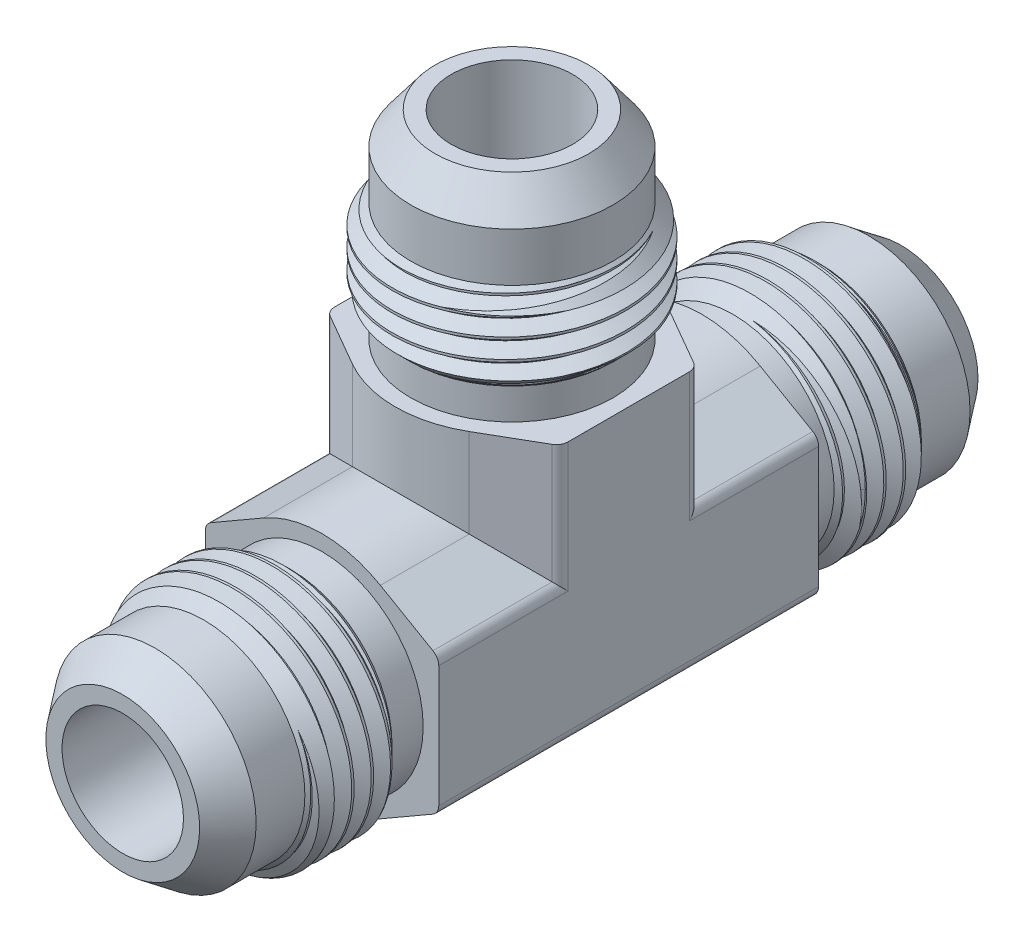
SolidWorks part; units mm, degrees
material "AISI 316 Annealed Stainless Steel Bar (SS)"
ref_plane "Front Plane" through (0, 0, 0) normal (0, 0, 1) x (1, 0, 0)
ref_plane "Top Plane" through (0, 0, 0) normal (0, 1, 0) x (1, 0, 0)
ref_plane "Right Plane" through (0, 0, 0) normal (1, 0, 0) x (0, 0, -1)
sketch "Sketch1" plane through (0, 0, 0) normal (1, 0, 0) x (0, 0, -1)
  line L0 (-31.75, -11.1125) -> (31.75, -11.1125) construction
  line L1 (31.75, -20.6375) -> (-31.75, -20.6375) construction
  line L2 (31.75, -20.6375) -> (31.75, 20.6375) construction
  line L3 (31.75, 20.6375) -> (-31.75, 20.6375) construction
  line L4 (-31.75, -20.6375) -> (-31.75, 20.6375) construction
  line L5 (31.75, -20.6375) -> (-31.75, 20.6375) construction
  line L6 (31.75, 20.6375) -> (-31.75, -20.6375) construction
  line L7 (0, -11.1125) -> (0, 20.6375) construction
  line L8 (-31.75, -4.8387) -> (-29.1209, -2.8575)
  line L9 (-15.494, -20.6375) -> (15.494, -20.6375)
  line L10 (-15.494, -20.6375) -> (-15.494, -1.5875)
  line L11 (-15.494, -1.5875) -> (15.494, -1.5875)
  line L12 (15.494, -20.6375) -> (15.494, -1.5875)
  line L13 (-15.494, -20.6375) -> (15.494, -1.5875) construction
  line L14 (-15.494, -1.5875) -> (15.494, -20.6375) construction
  line L15 (-31.75, -19.3675) -> (-15.494, -19.3675)
  line L16 (-31.75, -19.3675) -> (-31.75, -2.8575)
  line L17 (-31.75, -2.8575) -> (-15.494, -2.8575)
  line L18 (-15.494, -19.3675) -> (-15.494, -2.8575)
  line L19 (-31.75, -19.3675) -> (-15.494, -2.8575) construction
  line L20 (-31.75, -2.8575) -> (-15.494, -19.3675) construction
  line L21 (-18.034, -20.6375) -> (-25.146, -20.6375)
  line L22 (-18.034, -20.6375) -> (-18.034, -1.5875)
  line L23 (-18.034, -1.5875) -> (-25.146, -1.5875)
  line L24 (-25.146, -20.6375) -> (-25.146, -1.5875)
  line L25 (-18.034, -20.6375) -> (-25.146, -1.5875) construction
  line L26 (-18.034, -1.5875) -> (-25.146, -20.6375) construction
  line L27 (-31.75, -16.0655) -> (0, -16.0655)
  line L28 (-31.75, -16.0655) -> (-31.75, -6.1595)
  line L29 (-31.75, -6.1595) -> (0, -6.1595)
  line L30 (0, -16.0655) -> (0, -6.1595)
  line L31 (-31.75, -16.0655) -> (0, -6.1595) construction
  line L32 (-31.75, -6.1595) -> (0, -16.0655) construction
  line L33 (-31.75, -2.8575) -> (31.75, -2.8575) construction
  point P0 (0, 0)
  point P14 (-21.59, -11.1125)
  point P15 (-23.622, -11.1125)
  point P24 (-23.5585, -20.6375)
  point P25 (-15.875, -11.1125)
  point P30 (-22.0027, -20.6375)
  point P33 (31.75, -2.8575)
  dimension "Height" = 31.75
  dimension "Length" = 63.5
  dimension "Body Length" = 30.988
  dimension "Body Height" = 19.05
  dimension "Body Diameter" = 16.51
  dimension "Thread Size" = 19.05
  dimension "Space" = 2.54
  dimension "Thread Length" = 7.112
  dimension "Thread Pitch" = 1.5875
  dimension "ID" = 9.906
  dimension "Flared Angle" = 37
  dimension "Flare Height" = 1.9812
  dimension "D1" = 3.9688
sketch "Sketch2" plane through (0, 0, 0) normal (0, 0, 1) x (1, 0, 0)
  line L0 (9.525, -11.1125) -> (-9.525, -11.1125) construction
  line L1 (9.525, -20.6375) -> (-9.525, -20.6375)
  line L2 (9.525, -20.6375) -> (9.525, 20.6375)
  line L3 (9.525, 20.6375) -> (-9.525, 20.6375)
  line L4 (-9.525, -20.6375) -> (-9.525, 20.6375)
  line L5 (9.525, -20.6375) -> (-9.525, 20.6375) construction
  line L6 (9.525, 20.6375) -> (-9.525, -20.6375) construction
  circle A0 centre (0, -11.1125) radius 4.953
  point P0 (0, 0)
  point P12 (0, -16.0655)
  dimension "Width" = 19.05
sketch "Sketch3" plane through (0, 0, 0) normal (1, 0, 0) x (0, 0, -1)
  line L0 (-31.75, -11.1125) -> (0, -11.1125)
  line L1 (0, -11.1125) -> (0, -6.1595)
  line L2 (0, -6.1595) -> (-15.494, -6.1595)
  line L3 (-15.494, -20.6375) -> (-15.494, -1.5875) construction
  line L4 (-31.75, -6.1595) -> (0, -6.1595) construction
  line L5 (-15.494, -6.1595) -> (-15.494, -2.8575)
  line L6 (-15.494, -2.8575) -> (-18.034, -2.8575)
  line L7 (-31.75, -2.8575) -> (-15.494, -2.8575) construction
  line L8 (-18.034, -20.6375) -> (-18.034, -1.5875) construction
  line L9 (-18.034, -2.8575) -> (-19.304, -1.5875)
  line L10 (-18.034, -1.5875) -> (-25.146, -1.5875) construction
  line L11 (-19.304, -1.5875) -> (-23.876, -1.5875)
  line L12 (-23.876, -1.5875) -> (-25.146, -2.8575)
  line L13 (-25.146, -20.6375) -> (-25.146, -1.5875) construction
  line L14 (-25.146, -2.8575) -> (-29.1209, -2.8575)
  line L15 (-29.1209, -2.8575) -> (-31.75, -4.8387)
  line L16 (-31.75, -4.8387) -> (-31.75, -11.1125)
  dimension "D1" = 45
  dimension "D2" = 45
revolve "Revolve1" add sketch "Sketch3" angle 360 about L0
sketch "Sketch4" plane through (0, 0, 0) normal (0, 0, -1) x (-1, 0, 0)
  line L0 (-4.7625, -2.8636) -> (-9.0487, -5.3383)
  line L1 (9.525, -20.6375) -> (-9.525, -20.6375) construction
  line L2 (9.525, -20.6375) -> (9.525, -1.5875) construction
  line L3 (9.525, -1.5875) -> (-9.525, -1.5875) construction
  line L4 (-9.525, -20.6375) -> (-9.525, -1.5875) construction
  line L5 (9.525, -20.6375) -> (-9.525, -1.5875) construction
  line L6 (9.525, -1.5875) -> (-9.525, -20.6375) construction
  line L7 (0, -20.6375) -> (0, 20.6375) construction
  line L8 (-9.525, -6.1632) -> (-9.525, -16.0618)
  line L9 (-9.0488, -16.8867) -> (-4.7625, -19.3614)
  line L10 (4.7625, -19.3614) -> (9.0488, -16.8867)
  line L11 (9.525, -16.0618) -> (9.525, -6.1632)
  line L12 (9.0488, -5.3383) -> (4.7625, -2.8636)
  arc A0 (-4.7625, -2.8636) -> (4.7625, -2.8636) centre (0, -11.1125) cw
  arc A1 (-4.7625, -19.3614) -> (4.7625, -19.3614) centre (0, -11.1125) ccw
  arc A2 (9.525, -6.1632) -> (9.0488, -5.3383) centre (8.5725, -6.1632) ccw
  arc A3 (9.0488, -16.8867) -> (9.525, -16.0618) centre (8.5725, -16.0618) ccw
  arc A4 (-9.525, -16.0618) -> (-9.0488, -16.8867) centre (-8.5725, -16.0618) ccw
  arc A5 (-9.0487, -5.3383) -> (-9.525, -6.1632) centre (-8.5725, -6.1632) ccw
  point P0 (0, -11.1125)
  point P13 (9.525, -11.1125)
  point P17 (-9.525, -11.1125)
  point P20 (0, -0.114)
  point P26 (9.525, -5.6132)
  point P29 (9.525, -16.6118)
  point P32 (-9.525, -16.6118)
  point P35 (-9.525, -5.6132)
  dimension "D1" = 9.525
  dimension "D4" = 0.9525
  dimension "D2" = 120
  dimension "D3" = 120
extrude "Boss-Extrude1" add sketch "Sketch4" against normal up to vertex (15.494 mm away) up to point (0, -1.5875, 15.494)
pattern_circular "CirPattern1" count 3 every 90 about axis through (9.525, -11.1125, 0) along (-1, 0, 0) of bodies 105
combine bodies "Combine1" operation type add bodies to combine 106 107 105
sketch "Sketch5" plane through (0, 0, 0) normal (0, 0, 1) x (1, 0, 0)
  circle A0 centre (0, -11.1125) radius 4.953
extrude "Cut-Extrude1" cut sketch "Sketch5" against normal through all both and the other way through all
sketch "Sketch6" plane through (0, 20.6375, 0) normal (0, 1, 0) x (1, 0, 0)
  circle A0 centre (0, 0) radius 4.953
  dimension "D1" = 9.906
extrude "Cut-Extrude2" cut sketch "Sketch6" against normal up to vertex (31.75 mm away) up to point (0, -11.1125, 0)
ref_plane "Plane1" through (0, 0, 18.034) normal (0, 0, 1) x (1, 0, 0)
sketch "Sketch7" plane through (0, 0, 18.034) normal (0, 0, 1) x (1, 0, 0)
  circle A0 centre (0, -11.1125) radius 9.525 construction
  circle A1 centre (0, -11.1125) radius 9.525
curve "Helix/Spiral1" pitch 1.5875 height 8.6995 radius 9.525 centre (0, -11.1125, 18.034) axis (0, 0, 1) start towards (0, 1, 0)
sketch "Sketch8" plane through (0, 0, 0) normal (1, 0, 0) x (0, 0, -1)
  line L0 (-18.1332, -1.4156) -> (-16.5457, -1.4156) construction
  line L1 (-16.5457, -1.4156) -> (-17.3395, -2.7905) construction
  line L2 (-17.3395, -2.7905) -> (-18.1332, -1.4156) construction
  line L3 (-17.3395, -1.4156) -> (-17.3395, -1.5875) construction
  line L4 (-16.6449, -1.5875) -> (-18.034, -1.5875) construction
  line L5 (-17.4387, -2.6186) -> (-17.2402, -2.6186) construction
  line L6 (-17.3395, -2.6186) -> (-17.3395, -2.7905) construction
  line L7 (-17.3395, -1.5016) -> (-18.0836, -1.5016) construction
  line L8 (-16.5457, -1.4156) -> (-18.0836, -1.5016)
  line L9 (-18.0836, -1.5016) -> (-17.4387, -2.6186)
  line L10 (-17.4387, -2.6186) -> (-17.2402, -2.6186)
  line L11 (-17.2402, -2.6186) -> (-16.5457, -1.4156)
  dimension "D1" = 1.5875
  dimension "D2" = 0.1984
sweep "Cut-Sweep1" cut profiles "Sketch8" path "Helix/Spiral1" align with end faces yes
pattern_circular "CirPattern2" count 3 every 90 about axis through (9.525, -11.1125, 0) along (-1, 0, 0) of "Cut-Sweep1"
equation "\"D1@Sketch4\"=\"Width@Sketch2\"*.5"
equation "\"D4@Sketch4\"=\"Width@Sketch2\"*.05"
equation "\"D1@Sketch6\"=\"ID@Sketch1\""
equation "\"D4@Helix/Spiral1\"=\"Thread Pitch@Sketch1\""
equation "\"D3@Helix/Spiral1\"=\"Thread Length@Sketch1\"+\"Thread Pitch@Sketch1\""
equation "\"D1@Sketch8\"=\"Thread Pitch@Sketch1\""
equation "\"D2@Sketch8\"=\"D1@Sketch8\"/8"
equation "\"D1@Sketch1\"=\"Thread Pitch@Sketch1\"*2.5"
